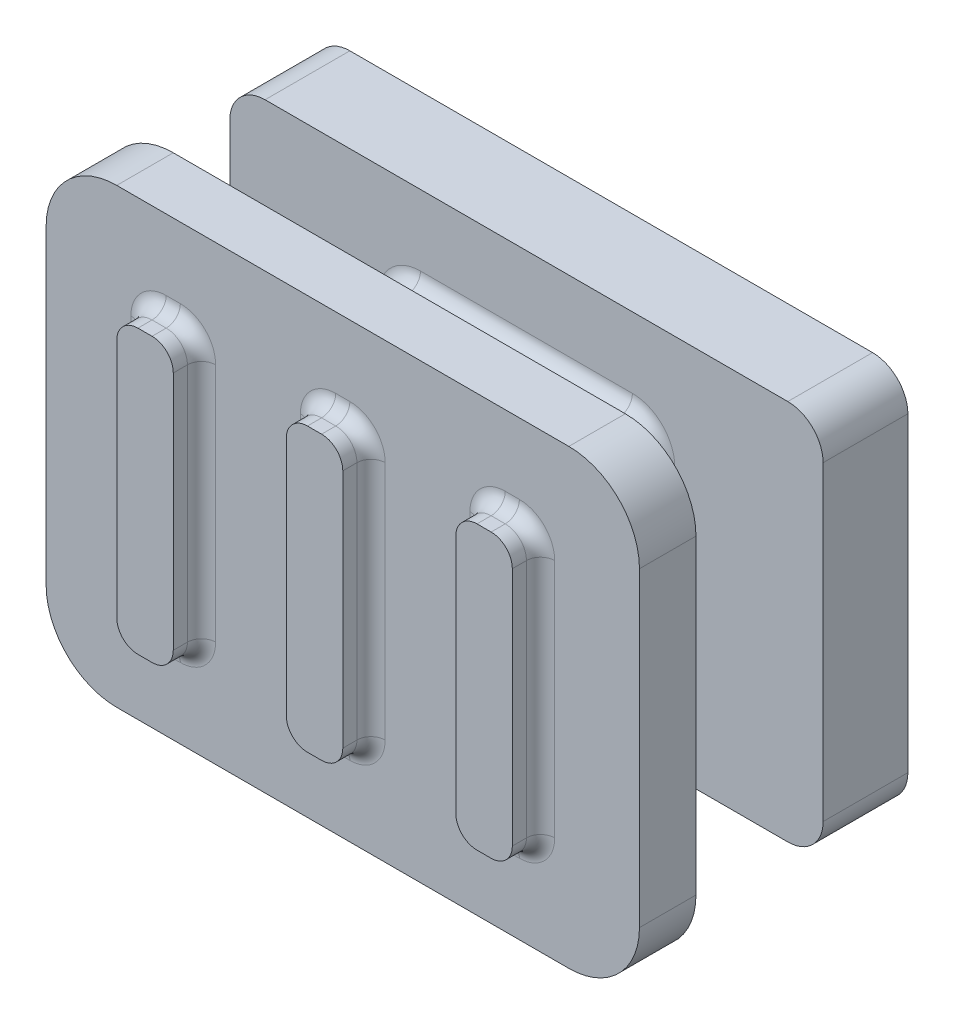
SolidWorks part; units mm, degrees
ref_plane "Спереди" through (0, 0, 0) normal (0, 0, 1) x (1, 0, 0)
ref_plane "Сверху" through (0, 0, 0) normal (0, 1, 0) x (1, 0, 0)
ref_plane "Справа" through (0, 0, 0) normal (1, 0, 0) x (0, 0, -1)
other "Configuration Table"
sketch "Slider_stem_profile" plane through (0, 0, 0) normal (0, 0, 1) x (1, 0, 0)
  line L0 (-1.5, -1.5) -> (1.5, -1.5)
  line L1 (1.9, -1.1) -> (1.9, 1.1)
  line L2 (1.5, 1.5) -> (-1.5, 1.5)
  line L3 (-1.9, 1.1) -> (-1.9, -1.1)
  arc A0 (1.5, -1.5) -> (1.9, -1.1) centre (1.5, -1.1) ccw
  arc A1 (1.9, 1.1) -> (1.5, 1.5) centre (1.5, 1.1) ccw
  arc A2 (-1.5, 1.5) -> (-1.9, 1.1) centre (-1.5, 1.1) ccw
  arc A3 (-1.9, -1.1) -> (-1.5, -1.5) centre (-1.5, -1.1) ccw
extrude "Slider_stem" add sketch "Slider_stem_profile" along normal blind 4.2 from offset 0
sketch "Captive_flange_profile" plane through (0, 0, 0) normal (0, 0, 1) x (1, 0, 0)
  line L0 (-3.7, -2.7) -> (3.7, -2.7)
  line L1 (4.2, -2.2) -> (4.2, 2.2)
  line L2 (3.7, 2.7) -> (-3.7, 2.7)
  line L3 (-4.2, 2.2) -> (-4.2, -2.2)
  arc A0 (3.7, -2.7) -> (4.2, -2.2) centre (3.7, -2.2) ccw
  arc A1 (4.2, 2.2) -> (3.7, 2.7) centre (3.7, 2.2) ccw
  arc A2 (-3.7, 2.7) -> (-4.2, 2.2) centre (-3.7, 2.2) ccw
  arc A3 (-4.2, -2.2) -> (-3.7, -2.7) centre (-3.7, -2.2) ccw
extrude "Captive_flange" add sketch "Captive_flange_profile" along normal blind 1.2 from offset 1.2
sketch "Thumb_pad_profile" plane through (0, 0, 0) normal (0, 0, 1) x (1, 0, 0)
  line L0 (-3.2, -3.2) -> (3.2, -3.2)
  line L1 (4.2, -2.2) -> (4.2, 2.2)
  line L2 (3.2, 3.2) -> (-3.2, 3.2)
  line L3 (-4.2, 2.2) -> (-4.2, -2.2)
  arc A0 (3.2, -3.2) -> (4.2, -2.2) centre (3.2, -2.2) ccw
  arc A1 (4.2, 2.2) -> (3.2, 3.2) centre (3.2, 2.2) ccw
  arc A2 (-3.2, 3.2) -> (-4.2, 2.2) centre (-3.2, 2.2) ccw
  arc A3 (-4.2, -2.2) -> (-3.2, -3.2) centre (-3.2, -2.2) ccw
extrude "Thumb_pad" add sketch "Thumb_pad_profile" along normal blind 0.8 from offset 4.2
sketch "Switch_pin_socket_profile" plane through (0, 0, 0) normal (0, 0, 1) x (1, 0, 0)
  line L0 (-0.8, -0.6) -> (0.8, -0.6)
  line L1 (0.9, -0.5) -> (0.9, 0.5)
  line L2 (0.8, 0.6) -> (-0.8, 0.6)
  line L3 (-0.9, 0.5) -> (-0.9, -0.5)
  arc A0 (0.8, -0.6) -> (0.9, -0.5) centre (0.8, -0.5) ccw
  arc A1 (0.9, 0.5) -> (0.8, 0.6) centre (0.8, 0.5) ccw
  arc A2 (-0.8, 0.6) -> (-0.9, 0.5) centre (-0.8, 0.5) ccw
  arc A3 (-0.9, -0.5) -> (-0.8, -0.6) centre (-0.8, -0.5) ccw
extrude "Switch_pin_socket" cut sketch "Switch_pin_socket_profile" against normal blind 2.4 from offset 2.3
sketch "PCB_edge_relief_profile" plane through (0, 0, 0) normal (0, 0, 1) x (1, 0, 0)
  line L0 (-2, 0.55) -> (2, 0.55)
  line L1 (2, 0.55) -> (2, 1.6)
  line L2 (2, 1.6) -> (-2, 1.6)
  line L3 (-2, 1.6) -> (-2, 0.55)
extrude "PCB_edge_relief" cut sketch "PCB_edge_relief_profile" against normal blind 0.7 from offset 0.6
fillet "Stem_shoulder_round" radius 0.2 24 edges at (1.7828, -1.3828, 1.2) (-1.7828, -1.3828, 1.2) (-1.7828, 1.3828, 1.2) (1.7828, 1.3828, 1.2) (1.7828, -1.3828, 2.4) (-1.7828, -1.3828, 2.4) (-1.7828, 1.3828, 2.4) (1.7828, 1.3828, 2.4) (-1.7828, -1.3828, 4.2) (-1.7828, 1.3828, 4.2) (1.7828, 1.3828, 4.2) (1.7828, -1.3828, 4.2) (0, 1.5, 1.2) (-1.9, 0, 1.2) (0, -1.5, 1.2) (1.9, 0, 1.2) (0, 1.5, 2.4) (-1.9, 0, 2.4) (0, -1.5, 2.4) (1.9, 0, 2.4) (1.9, 0, 4.2) (0, 1.5, 4.2) (-1.9, 0, 4.2) (0, -1.5, 4.2)
sketch "Thumb_rib_0_profile" plane through (0, 0, 0) normal (0, 0, 1) x (1, 0, 0)
  line L0 (-2.5, -2) -> (-2.3, -2)
  line L1 (-2, -1.7) -> (-2, 1.7)
  line L2 (-2.3, 2) -> (-2.5, 2)
  line L3 (-2.8, 1.7) -> (-2.8, -1.7)
  arc A0 (-2.3, -2) -> (-2, -1.7) centre (-2.3, -1.7) ccw
  arc A1 (-2, 1.7) -> (-2.3, 2) centre (-2.3, 1.7) ccw
  arc A2 (-2.5, 2) -> (-2.8, 1.7) centre (-2.5, 1.7) ccw
  arc A3 (-2.8, -1.7) -> (-2.5, -2) centre (-2.5, -1.7) ccw
extrude "Thumb_rib_0" add sketch "Thumb_rib_0_profile" along normal blind 0.5 from offset 4.9
sketch "Thumb_rib_1_profile" plane through (0, 0, 0) normal (0, 0, 1) x (1, 0, 0)
  line L0 (-0.1, -2) -> (0.1, -2)
  line L1 (0.4, -1.7) -> (0.4, 1.7)
  line L2 (0.1, 2) -> (-0.1, 2)
  line L3 (-0.4, 1.7) -> (-0.4, -1.7)
  arc A0 (0.1, -2) -> (0.4, -1.7) centre (0.1, -1.7) ccw
  arc A1 (0.4, 1.7) -> (0.1, 2) centre (0.1, 1.7) ccw
  arc A2 (-0.1, 2) -> (-0.4, 1.7) centre (-0.1, 1.7) ccw
  arc A3 (-0.4, -1.7) -> (-0.1, -2) centre (-0.1, -1.7) ccw
extrude "Thumb_rib_1" add sketch "Thumb_rib_1_profile" along normal blind 0.5 from offset 4.9
sketch "Thumb_rib_2_profile" plane through (0, 0, 0) normal (0, 0, 1) x (1, 0, 0)
  line L0 (2.3, -2) -> (2.5, -2)
  line L1 (2.8, -1.7) -> (2.8, 1.7)
  line L2 (2.5, 2) -> (2.3, 2)
  line L3 (2, 1.7) -> (2, -1.7)
  arc A0 (2.5, -2) -> (2.8, -1.7) centre (2.5, -1.7) ccw
  arc A1 (2.8, 1.7) -> (2.5, 2) centre (2.5, 1.7) ccw
  arc A2 (2.3, 2) -> (2, 1.7) centre (2.3, 1.7) ccw
  arc A3 (2, -1.7) -> (2.3, -2) centre (2.3, -1.7) ccw
extrude "Thumb_rib_2" add sketch "Thumb_rib_2_profile" along normal blind 0.5 from offset 4.9
fillet "Thumb_rib_root_round" radius 0.2 24 edges at (2.0879, -1.9121, 5) (2.4, -2, 5) (2.7121, -1.9121, 5) (2.7121, 1.9121, 5) (2.4, 2, 5) (2.0879, 1.9121, 5) (-0.3121, -1.9121, 5) (0, -2, 5) (0.3121, -1.9121, 5) (0.3121, 1.9121, 5) (0, 2, 5) (-0.3121, 1.9121, 5) (-2.7121, -1.9121, 5) (-2.4, -2, 5) (-2.0879, -1.9121, 5) (-2.0879, 1.9121, 5) (-2.4, 2, 5) (-2.7121, 1.9121, 5) (2.8, 0, 5) (2, 0, 5) (0.4, 0, 5) (-0.4, 0, 5) (-2, 0, 5) (-2.8, 0, 5)
